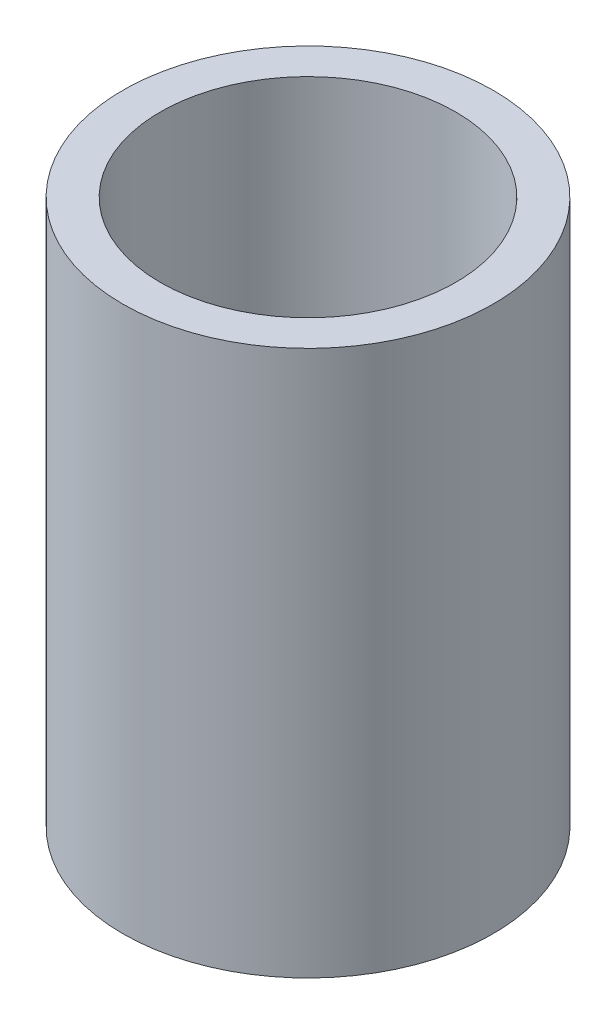
SolidWorks part; units mm, degrees
ref_plane "Front Plane" through (0, 0, 0) normal (0, 0, 1) x (1, 0, 0)
ref_plane "Top Plane" through (0, 0, 0) normal (0, 1, 0) x (1, 0, 0)
ref_plane "Right Plane" through (0, 0, 0) normal (1, 0, 0) x (0, 0, -1)
sketch "Sketch1" plane through (0, 0, 0) normal (0, 1, 0) x (1, 0, 0)
  circle A0 centre (0, 0) radius 27.5
  dimension "SLEEVE_OD" = 55
extrude "Boss-Extrude1" add sketch "Sketch1" along normal blind 80.9711
sketch "Sketch2" plane through (0, 0, 0) normal (0, 1, 0) x (1, 0, 0)
  circle A0 centre (0, 0) radius 21.9324
  dimension "BORE_D" = 43.8648
extrude "Cut-Extrude1" cut sketch "Sketch2" along normal through all
chamfer "Chamfer1" distance 3.4217 angle 60 rebuild error yes
